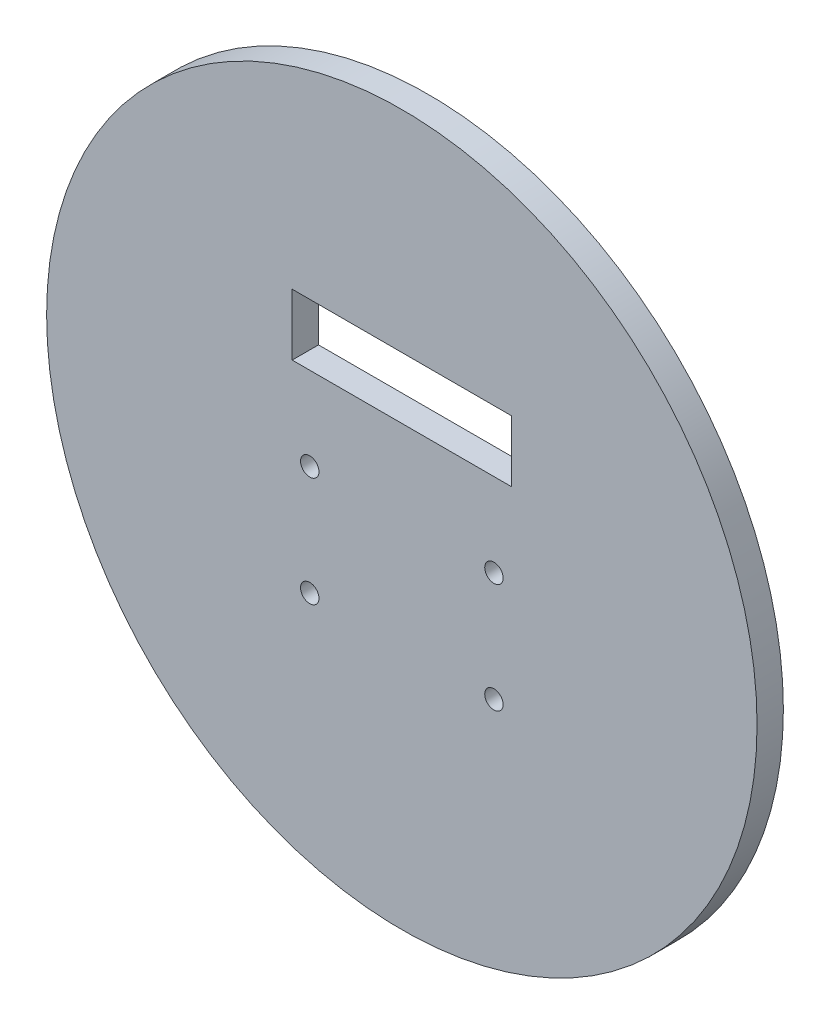
SolidWorks part; units mm, degrees
ref_plane "Plan de face" through (0, 0, 0) normal (0, 0, 1) x (1, 0, 0)
ref_plane "Plan de dessus" through (0, 0, 0) normal (0, 1, 0) x (1, 0, 0)
ref_plane "Plan de droite" through (0, 0, 0) normal (1, 0, 0) x (0, 0, -1)
sketch "Esquisse1" plane through (0, 0, 0) normal (0, 0, 1) x (1, 0, 0)
  line L0 (0, 0) -> (-10.5, 0) construction
  line L1 (-10.5, 0) -> (-10.5, -12.5) construction
  line L2 (-10.5, -12.5) -> (10.5, -12.5) construction
  line L3 (10.5, -12.5) -> (10.5, 0) construction
  line L4 (10.5, 0) -> (0, 0) construction
  circle A0 centre (0, 0) radius 40.5
  circle A1 centre (-10.5, -12.5) radius 1.05
  circle A2 centre (10.5, -12.5) radius 1.05
  circle A3 centre (-10.5, 0) radius 1.05
  circle A4 centre (10.5, 0) radius 1.05
  dimension "D1" = 81
  dimension "D6" = 2.1
  dimension "D7" = 2.1
  dimension "D8" = 2.1
  dimension "D9" = 2.1
  dimension "D2" = 10.5
  dimension "D3" = 10.5
  dimension "D4" = 12.5
  dimension "D5" = 21
extrude "Boss.-Extru.1" add sketch "Esquisse1" along normal blind 3
sketch "Esquisse2" plane through (0, 0, 0) normal (0, 0, 1) x (1, 0, 0)
  line L1 (12.5, 9.5) -> (-12.5, 9.5)
  line L2 (12.5, 9.5) -> (12.5, -14.5)
  line L3 (12.5, -14.5) -> (-12.5, -14.5)
  line L4 (-12.5, 9.5) -> (-12.5, -14.5)
  line L6 (0, 4) -> (0, -14.5)
  line L7 (12.5, 9.5) -> (-12.5, 9.5)
  line L8 (12.5, 9.5) -> (12.5, 16.5)
  line L9 (12.5, 16.5) -> (-12.5, 16.5)
  line L10 (-12.5, 9.5) -> (-12.5, 16.5)
  line L11 (12.5, 9.5) -> (-12.5, 9.5)
  line L12 (12.5, 9.5) -> (12.5, 4)
  line L14 (-12.5, 9.5) -> (-12.5, 4)
  line L15 (12.5, 9.5) -> (-12.5, 9.5)
  line L16 (12.5, 9.5) -> (12.5, 4)
  line L17 (12.5, 4) -> (-12.5, 4)
  line L18 (-12.5, 9.5) -> (-12.5, 4)
  circle A0 centre (10.5, -12.5) radius 1.05 construction
  point P14 (0, 0)
  point P16 (12.5, -12.1537)
  dimension "D1" = 24
  dimension "D2" = 25
  dimension "D3" = 2
  dimension "D4" = 2
  dimension "D5" = 25
  dimension "D6" = 7
  dimension "D7" = 18.5
extrude "Enlèv. mat.-Extru.4" cut sketch "Esquisse2" along normal blind 14 contours L10 L1 L8 L9 region at (0, 13, 0)
extrude "Boss.-Extru.6" add sketch "Esquisse2<7>" against normal blind 2 contours L17 L2 L1 L4 region at (0, 6.75, 0)
sketch "Esquisse2<7>" plane through (0, 0, 0) normal (0, 0, 1) x (1, 0, 0) same geometry as "Esquisse2"
extrude "Enlèv. mat.-Extru.5" cut sketch "Esquisse2<8>" against normal blind 2 contours L17 L2 L1 L4 region at (0, 6.75, 0)
sketch "Esquisse2<8>" plane through (0, 0, 0) normal (0, 0, 1) x (1, 0, 0) same geometry as "Esquisse2"
extrude "Boss.-Extru.7" add sketch "Esquisse2<9>" against normal blind 2 contours L2 L17 L6 L3 | L6 L17 L4 L3 region at (6.25, -5.25, 0) region at (-6.25, -5.25, 0)
sketch "Esquisse2<9>" plane through (0, 0, 0) normal (0, 0, 1) x (1, 0, 0) same geometry as "Esquisse2"
sketch "Esquisse7" plane through (0, 0, 0) normal (0, 0, 1) x (1, 0, 0)
  circle A0 centre (-10.5, 0) radius 1.05
  circle A1 centre (-10.5, -12.5) radius 1.05
  circle A2 centre (10.5, 0) radius 1.05
  circle A3 centre (10.5, -12.5) radius 1.05
  dimension "D1" = 2.1
  dimension "D2" = 2.1
  dimension "D3" = 2.1
  dimension "D4" = 2.1
extrude "Enlèv. mat.-Extru.6" cut sketch "Esquisse7" against normal through all both and the other way through all
